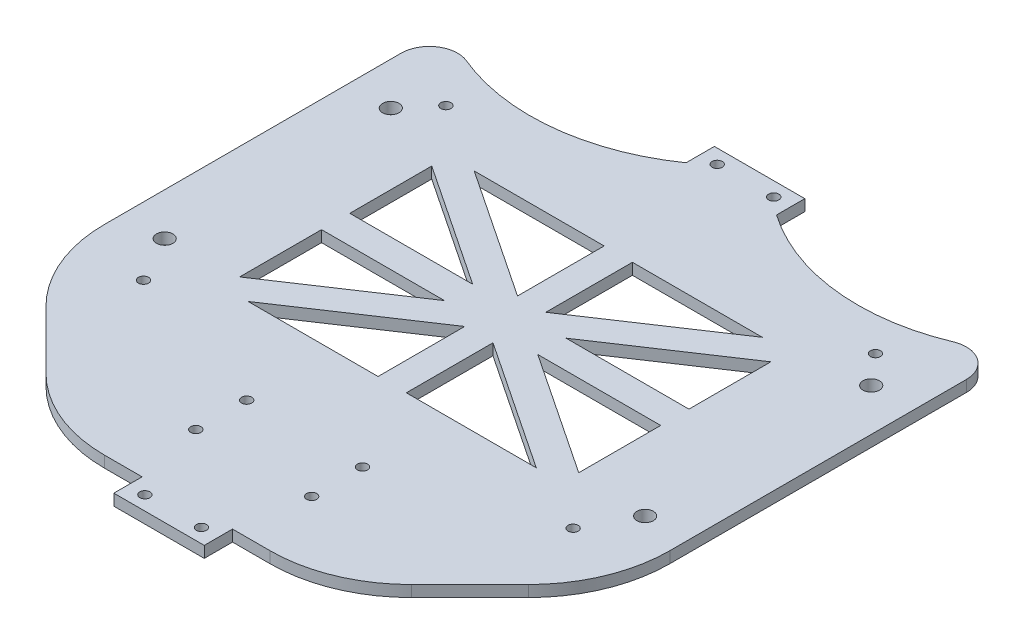
SolidWorks part; units mm, degrees
material "PBT General Purpose"
ref_plane "Front Plane" through (0, 0, 0) normal (0, 0, 1) x (1, 0, 0)
ref_plane "Top Plane" through (0, 0, 0) normal (0, 1, 0) x (1, 0, 0)
ref_plane "Right Plane" through (0, 0, 0) normal (1, 0, 0) x (0, 0, -1)
sketch "Sketch1" plane through (0, 0, 0) normal (0, 1, 0) x (1, 0, 0)
  line L0 (-100, -222) -> (100, -222)
  line L1 (100, -222) -> (100, -29.5)
  line L2 (100, -29.5) -> (16, -29.5) construction
  line L3 (16, -29.5) -> (16, -19.5)
  line L10 (-16, -29.5) -> (-100, -29.5) construction
  line L11 (-100, -29.5) -> (-100, -222)
  line L12 (0, -222) -> (0, 5.5) construction
  line L17 (-10, -24.5) -> (10, -24.5) construction
  line L18 (-16, -29.5) -> (16, -29.5) construction
  line L19 (-10, -227) -> (10, -227) construction
  line L20 (-16.5139, -104.5) -> (-60, -104.5)
  line L21 (-60, -114.5) -> (-16.5139, -114.5)
  line L22 (-5, -118.8426) -> (-5, -149.5)
  line L27 (5, -118.8426) -> (5, -149.5)
  line L28 (60, -109.5) -> (-60, -109.5) construction
  line L29 (60, -114.5) -> (16.5139, -114.5)
  line L30 (16.5139, -104.5) -> (60, -104.5)
  line L31 (5, -100.1574) -> (5, -69.5)
  line L32 (-5, -100.1574) -> (-5, -69.5)
  line L54 (-60, -69.5) -> (-60, -149.5)
  line L55 (-60, -149.5) -> (60, -149.5)
  line L56 (60, -149.5) -> (60, -69.5)
  line L57 (60, -69.5) -> (-60, -69.5)
  line L59 (-16, -19.5) -> (16, -19.5)
  line L61 (-16, -222) -> (-16, -232)
  line L62 (-16, -232) -> (16, -232)
  line L63 (16, -232) -> (16, -222)
  line L64 (17, -183) -> (17, -210)
  line L65 (17, -210) -> (-18, -210)
  line L66 (-18, -210) -> (-18, -183)
  line L67 (-18, -183) -> (17, -183)
  line L68 (-21, -198) -> (-21, -180) construction
  line L69 (-21, -180) -> (20, -180) construction
  line L70 (20, -180) -> (20, -198) construction
  line L74 (-60, -75.5093) -> (50.9861, -149.5)
  line L75 (60, -143.4907) -> (-50.9861, -69.5)
  line L76 (-60, -143.4907) -> (50.9861, -69.5)
  line L77 (-50.9861, -149.5) -> (60, -75.5093)
  line L78 (60, -69.5) -> (-60, -149.5) construction
  line L79 (-60, -69.5) -> (60, -149.5) construction
  line L81 (-16, -19.5) -> (-16, -29.5)
  arc A11 (16, -29.5) -> (100, -29.5) centre (58, 30.5) ccw
  arc A12 (-16, -29.5) -> (-100, -29.5) centre (-58, 30.5) cw
  point P5 (-76, -161.5)
  point P6 (-76, -54.5)
  point P7 (76, -161.5)
  point P8 (76, -54.5)
  point P10 (-10, -24.5)
  point P11 (10, -24.5)
  point P12 (0, -222)
  point P27 (0, -109.5)
  point P37 (0, -109.5)
  point P53 (0, -232)
  point P58 (-21, -180)
  point P59 (-21, -198)
  point P60 (20, -180)
  point P62 (20, -198)
  point P69 (-0.5, -180)
  point P70 (-0.5, -183)
  point P131 (-85, -65)
  point P132 (-85, -145)
  point P133 (85, -145)
  point P134 (85, -65)
  dimension "D29" = 22
  dimension "D30" = 10
  dimension "D31" = 27
  dimension "D39" = 3
  dimension "D12" = 152
  dimension "D13" = 60
  dimension "D4" = 200
  dimension "D8" = 30.5
  dimension "D9" = 192.5
  dimension "D10" = 10
  dimension "D11" = 16
  dimension "D14" = 107
  dimension "D15" = 25
  dimension "D16" = 20
  dimension "D17" = 5
  dimension "D18" = 20
  dimension "D19" = 40
  dimension "D20" = 10
  dimension "D21" = 10
  dimension "D32" = 35
  dimension "D33" = 17
  dimension "D37" = 18
  dimension "D38" = 41
  dimension "D58" = 120
  dimension "D60" = 80
  dimension "D67" = 80
  dimension "D68" = 170
  dimension "D69" = 77
  dimension "D75" = 10
  dimension "D76" = 10
extrude "Boss-Extrude1" add sketch "Sketch1" along normal blind 4 contours L12 | L12 | A12 L11 L0 L1 A11 L3 L57 L56 L55 L54 | L74 L76 L75 L57 L54 | L74 L77 L75 L76 | L77 L74 L55 L56 L75 | L55 L77 L74 L76 L54 | L75 L77 L56 L57 L76 | L62 L63 L0 L61 | L21 L76 L74 L20 L54 | L75 L76 L31 L57 L32 | L77 L75 L29 L56 L30 | L77 L22 L55 L27 L74 | L67 L66 L65 L64 region at (-97.1538, 0, 125.75) region at (0, 0, 227) region at (-36.3323, 0, 109.5) region at (-31.1426, 0, 88.7382) region at (0, 0, 109.5) region at (-31.1426, 0, 130.2618) region at (31.1426, 0, 130.2618) region at (0, 0, 133.3236) region at (31.1426, 0, 88.7382) region at (0, 0, 85.6764) region at (36.3323, 0, 109.5) region at (-0.5, 0, 196.5)
hole_wizard "M5 Clearance Hole1" positions "Sketch15" profile "Sketch14" hole size "M5" standard "ISO" end condition through all
sketch "Sketch15" plane through (0, 4, 0) normal (0, 1, 0) x (1, 0, 0)
  point P0 (-85, -65)
  point P3 (-85, -145)
  point P6 (85, -145)
  point P9 (85, -65)
sketch "Sketch14" plane through (-85, 4, 65) normal (1, 0, 0) x (0, 0, 1)
  line L0 (0, 0) -> (0, 4)
  line L1 (0, 4) -> (2.9, 4)
  line L2 (2.9, 4) -> (2.9, 0)
  line L5 (2.9, 0) -> (0, 0)
  line L11 (0, -6.35) -> (0, 107.95) construction
  dimension "Thru Hole Dia." = 5.8
  dimension "Thru Hole Depth" = 4
fillet "Fillet1" radius 10 2 edges at (100, 2, 29.5) (-100, 2, 29.5)
hole_wizard "M3 Clearance Hole1" positions "Sketch16" profile "Sketch17" hole size "M3" standard "ISO"
sketch "Sketch16" plane through (0, 4, 0) normal (0, 1, 0) x (1, 0, 0)
  point P0 (-21, -198)
  point P3 (-21, -180)
  point P6 (20, -180)
  point P9 (20, -198)
sketch "Sketch17" plane through (-21, 4, 198) normal (1, 0, 0) x (0, 0, 1)
  line L0 (0, 0) -> (0, 11.0815)
  line L1 (0, 11.0815) -> (1.8, 10)
  line L2 (1.8, 10) -> (1.8, 0)
  line L5 (1.8, 0) -> (0, 0)
  line L10 (0, 11.0815) -> (-1.8, 10) construction
  line L11 (0, -6.35) -> (0, 107.95) construction
  dimension "Hole Dia." = 3.6
  dimension "Hole Depth" = 10
  dimension "Drill Angle" = 118
chamfer "Chamfer1" distance 50 angle 45 2 edges at (100, 2, 222) (-100, 2, 222)
fillet "Fillet3" radius 50 4 edges at (-100, 2, 172) (-50, 2, 222) (100, 2, 172) (50, 2, 222)
hole_wizard "M3 Clearance Hole2" positions "Sketch18" profile "Sketch19" hole size "M3" standard "ISO" end condition through all
sketch "Sketch18" plane through (0, 4, 0) normal (0, 1, 0) x (1, 0, 0)
  point P0 (-76, -54.5)
  point P3 (76, -54.5)
  point P6 (76, -161.5)
  point P9 (-76, -161.5)
  point P12 (-10, -24.5)
  point P15 (10, -24.5)
  point P19 (-10, -227)
  point P22 (10, -227)
sketch "Sketch19" plane through (-76, 4, 54.5) normal (1, 0, 0) x (0, 0, 1)
  line L0 (0, 0) -> (0, 4)
  line L1 (0, 4) -> (1.8, 4)
  line L2 (1.8, 4) -> (1.8, 0)
  line L5 (1.8, 0) -> (0, 0)
  line L11 (0, -6.35) -> (0, 107.95) construction
  dimension "Thru Hole Dia." = 3.6
  dimension "Thru Hole Depth" = 4
equation "\"w9\"=2"
